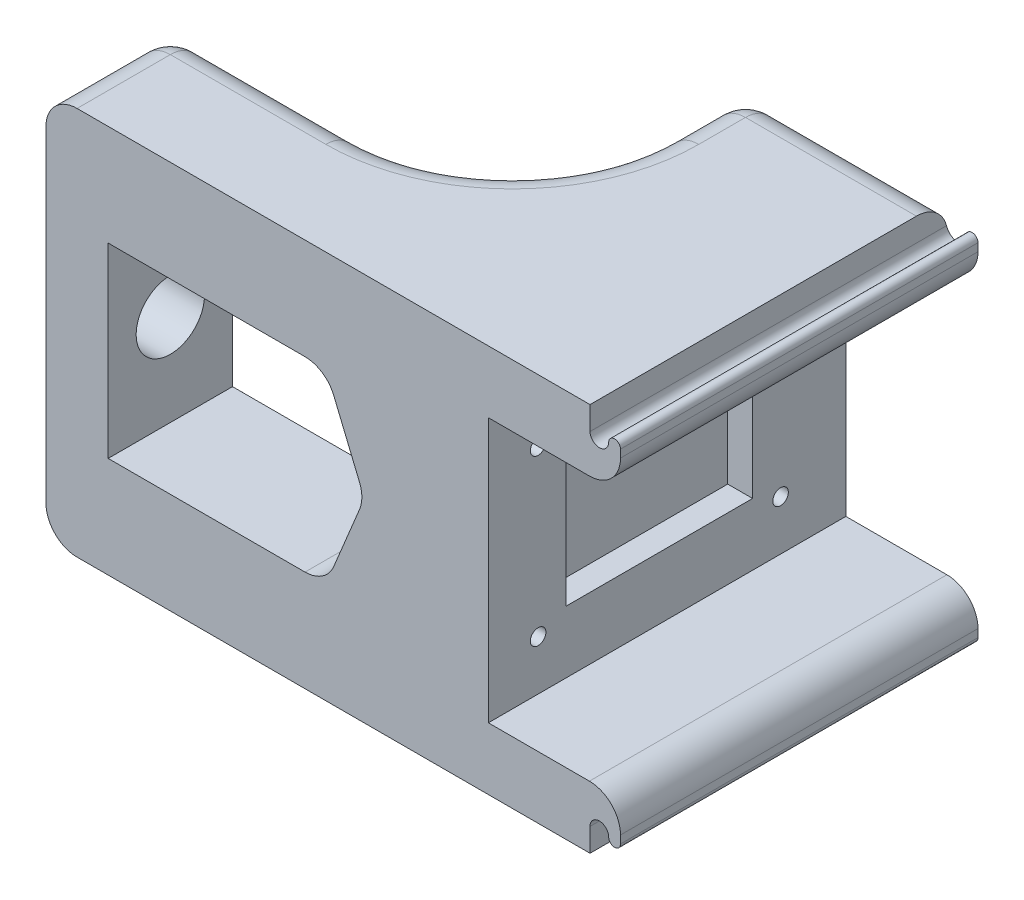
SolidWorks part; units mm, degrees
ref_plane "Přední rovina" through (0, 0, 0) normal (0, 0, 1) x (1, 0, 0)
ref_plane "Horní rovina" through (0, 0, 0) normal (0, 1, 0) x (1, 0, 0)
ref_plane "Pravá rovina" through (0, 0, 0) normal (1, 0, 0) x (0, 0, -1)
sketch "Skica1" plane through (0, 0, 0) normal (0, 0, 1) x (1, 0, 0)
  line L0 (0, 0) -> (0, 25)
  line L1 (0, 25) -> (35, 25)
  line L2 (35, 25) -> (35, 0)
  line L3 (35, 0) -> (0, 0)
  line L4 (4, 18.5) -> (4, 6.5)
  line L5 (4, 6.5) -> (18, 6.5)
  line L6 (18, 6.5) -> (20.4853, 12.5)
  line L7 (20.4853, 12.5) -> (18, 18.5)
  line L8 (18, 18.5) -> (4, 18.5)
  point P7 (4, 12.5)
  point P11 (0, 12.5)
  dimension "D1" = 25
  dimension "D2" = 12
  dimension "D3" = 4
  dimension "D4" = 14
  dimension "D5" = 14
  dimension "D6" = 135
  dimension "D7" = 35
extrude "Přidat vysunutím1" add sketch "Skica1" along normal blind 8
sketch "Skica2" plane through (0, 0, 0) normal (-1, 0, 0) x (0, 0, 1)
  line L0 (8, 25) -> (0, 25) construction
  line L1 (0, 25) -> (0, 0) construction
  circle A0 centre (4, 12.5) radius 2.2
  point P5 (4, 25)
  point P9 (0, 12.5)
  dimension "D1" = 4.4
extrude "Odebrat vysunutím1" cut sketch "Skica2" against normal blind 8
sketch "Skica3" plane through (0, 0, 0) normal (0, 0, -1) x (-1, 0, 0)
  line L0 (0, 0) -> (-35, 0) construction
  line L1 (-35, 25) -> (-22, 25)
  line L2 (-35, 25) -> (-35, 0)
  line L3 (-35, 0) -> (-22, 0)
  line L4 (-22, 25) -> (-22, 0)
  line L5 (-4, 18.5) -> (-4, 6.5) construction
  dimension "D1" = 18
extrude "Přidat vysunutím3" add sketch "Skica3" along normal blind 15
fillet "Zaoblit3" radius 10 1 edges at (22, 12.5, 0)
fillet "Zaoblit5" radius 2 1 edges at (0, 12.5, 0)
fillet "Zaoblit6" radius 2 5 edges at (0, 0, 5) (0.5858, 0, 0.5858) (7, 0, 0) (19.0711, 0, -2.9289) (22, 0, -12.5)
fillet "Zaoblit7" radius 2 5 edges at (0, 25, 5) (0.5858, 25, 0.5858) (7, 25, 0) (19.0711, 25, -2.9289) (22, 25, -12.5)
sketch "Skica6" plane through (0, 0, -15) normal (0, 0, -1) x (-1, 0, 0)
  line L0 (-35, 23.5) -> (-35, 1.5)
  line L1 (-35, 25) -> (-35, 0) construction
  line L2 (-36.96, 23.5) -> (-36.96, 1.5)
  arc A0 (-35, 23.5) -> (-36.2, 23.5) centre (-35.6, 23.5) cw
  arc A1 (-36.2, 23.5) -> (-36.96, 23.5) centre (-36.58, 23.5) ccw
  arc A2 (-35, 1.5) -> (-36.2, 1.5) centre (-35.6, 1.5) ccw
  arc A3 (-36.2, 1.5) -> (-36.96, 1.5) centre (-36.58, 1.5) cw
  dimension "D1" = 1.5
  dimension "D3" = 0.6
  dimension "D4" = 0.38
  dimension "D5" = 0.6
  dimension "D6" = 0.38
  dimension "D2" = 1.5
extrude "Přidat vysunutím6" add sketch "Skica6" against normal blind 23
fillet "Zaoblit12" radius 2 5 edges at (29.5, 0, -15) (22.5858, 0.5858, -15) (29.5, 25, -15) (22.5858, 24.4142, -15) (22, 12.5, -15)
fillet "Zaoblit13" radius 2 1 edges at (20.4853, 12.5, 1.6458)
fillet "Zaoblit14" radius 2 1 edges at (18, 18.5, 3)
fillet "Zaoblit15" radius 2 1 edges at (18, 6.5, 3)
sketch "Skica7" plane through (36.96, 0, 0) normal (1, 0, 0) x (0, 0, -1)
  line L0 (-8, 23.5) -> (-8, 1.5) construction
  line L1 (-8, 21) -> (15, 21)
  line L2 (-8, 21) -> (-8, 4)
  line L3 (-8, 4) -> (15, 4)
  line L4 (15, 21) -> (15, 4)
  line L5 (-8, 23.5) -> (15, 23.5) construction
  dimension "D1" = 23
  dimension "D2" = 0
  dimension "D3" = 17
  dimension "D4" = 2.5
extrude "Odebrat vysunutím4" cut sketch "Skica7" against normal blind 8.5
fillet "Zaoblit18" radius 2 1 edges at (36.96, 21, -3.5)
fillet "Zaoblit19" radius 2 1 edges at (36.96, 4, -3.5)
sketch "Skica8" plane through (28.46, 0, 0) normal (1, 0, 0) x (0, 0, -1)
  line L0 (-8, 21) -> (-8, 4) construction
  line L1 (-3, 17) -> (9, 17)
  line L2 (-3, 17) -> (-3, 8)
  line L3 (-3, 8) -> (9, 8)
  line L4 (9, 17) -> (9, 8)
  circle A0 centre (-4.8, 17.8) radius 0.5
  circle A1 centre (-4.8, 7.2) radius 0.5
  circle A2 centre (10.8, 17.8) radius 0.5
  circle A3 centre (10.8, 7.2) radius 0.5
  point P7 (-8, 12.5)
  point P8 (-3, 12.5)
  point P17 (0, 0)
  point P18 (0, 0)
  point P19 (0, 0)
  point P20 (0, 0)
  point P21 (-4.8, 7.3275)
  dimension "D4" = 1
  dimension "D5" = 1
  dimension "D6" = 1
  dimension "D7" = 1
  dimension "D1" = 9
  dimension "D2" = 12
  dimension "D3" = 5
  dimension "D8" = 0.8
  dimension "D9" = 1.8
  dimension "D10" = 1.8
  dimension "D11" = 0.8
extrude "Odebrat vysunutím5" cut sketch "Skica8" against normal blind 1.6
